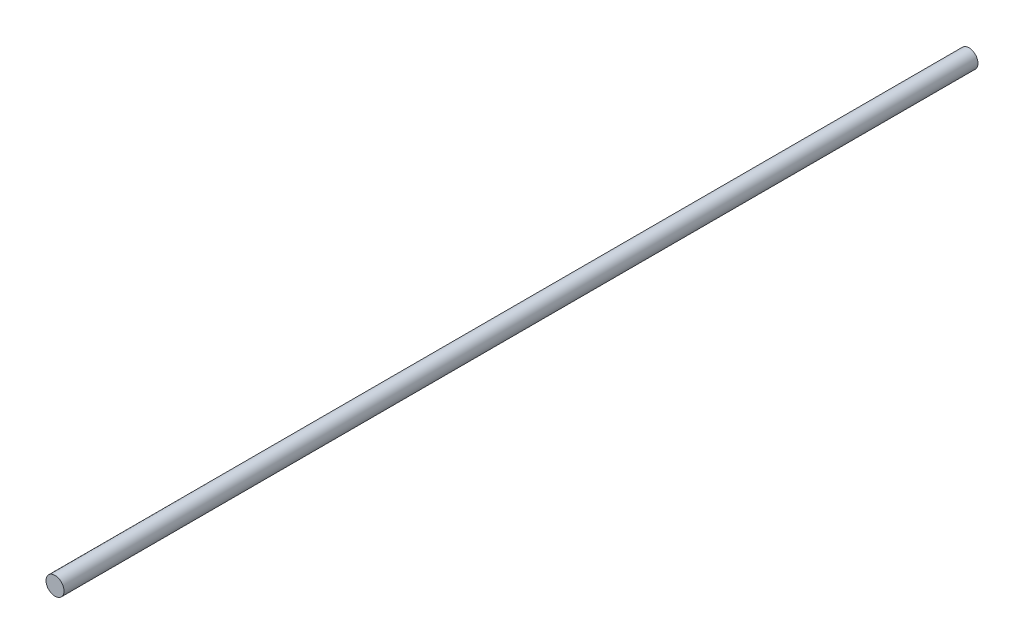
SolidWorks part; units mm, degrees
material "AISI 316 Stainless Steel Sheet (SS)"
ref_plane "Front (1)" through (0, 0, 0) normal (0, 0, 1) x (1, 0, 0)
ref_plane "Top (2)" through (0, 0, 0) normal (0, 1, 0) x (1, 0, 0)
ref_plane "Right (3)" through (0, 0, 0) normal (1, 0, 0) x (0, 0, -1)
ref_axis "X Axis" through (13.5064, 0, 0) along (-1, 0, 0)
ref_axis "Y Axis" through (0, 12.3593, 0) along (0, -1, 0)
ref_axis "Z Axis" through (0, 0, 14.1119) along (0, 0, -1)
sketch "Sketch2" plane through (0, 0, 0) normal (1, 0, 0) x (0, 0, -1)
  line L1 (0, 0) -> (405, 0)
  line L2 (0, 0) -> (0, 4)
  line L3 (0, 4) -> (405, 4)
  line L4 (405, 0) -> (405, 4)
  dimension "D1" = 405
  dimension "D2" = 4
revolve "Revolve1" add sketch "Sketch2" angle 360 about L1
cosmetic thread "Cosmetic Thread2" parameters "D2"=6.891
